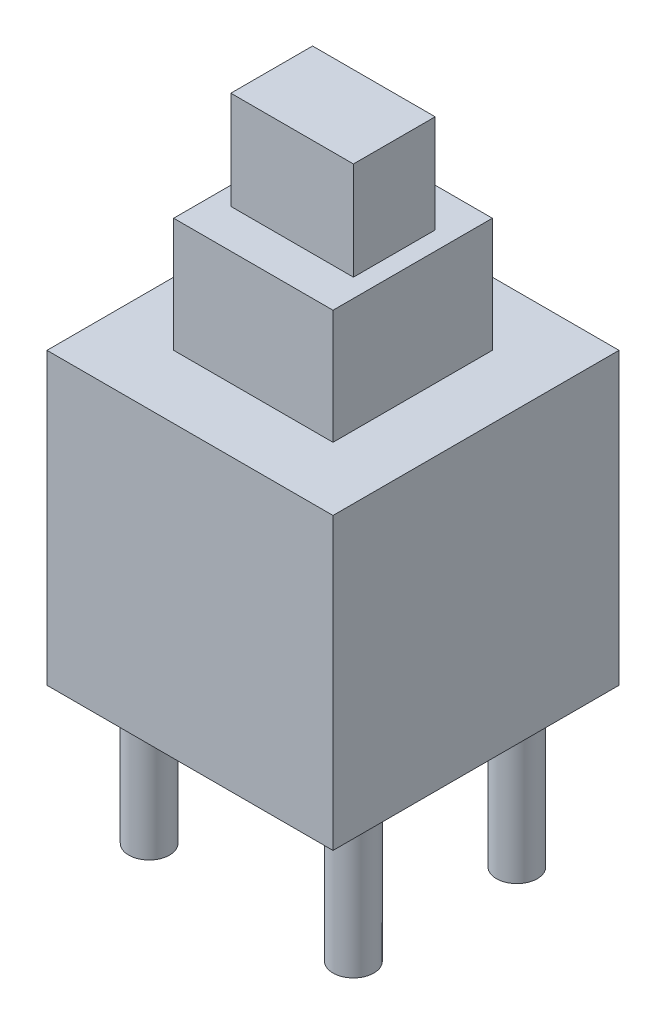
SolidWorks part; units mm, degrees
ref_plane "前视基准面" through (0, 0, 0) normal (0, 0, 1) x (1, 0, 0)
ref_plane "上视基准面" through (0, 0, 0) normal (0, 1, 0) x (1, 0, 0)
ref_plane "右视基准面" through (0, 0, 0) normal (1, 0, 0) x (0, 0, -1)
other "Configuration Table"
sketch "草图1" plane through (0, 0, 0) normal (0, 1, 0) x (1, 0, 0)
  line L1 (0, 0) -> (7, 0)
  line L2 (0, 0) -> (0, 7)
  line L3 (0, 7) -> (7, 7)
  line L4 (7, 0) -> (7, 7)
  dimension "D1" = 7
  dimension "D2" = 7
extrude "凸台-拉伸1" add sketch "草图1" along normal blind 7.1
sketch "草图2" plane through (0, 7.1, 0) normal (0, 1, 0) x (1, 0, 0)
  line L0 (3.5, 7) -> (3.5, 0) construction
  line L1 (7, 7) -> (0, 7) construction
  line L2 (0, 0) -> (7, 0) construction
  line L3 (1.55, 5.45) -> (5.45, 1.55) construction
  line L4 (1.55, 5.45) -> (5.45, 5.45)
  line L5 (1.55, 5.45) -> (1.55, 1.55)
  line L6 (1.55, 1.55) -> (5.45, 1.55)
  line L7 (5.45, 5.45) -> (5.45, 1.55)
  point P10 (3.5, 3.5)
  dimension "D1" = 3.9
extrude "凸台-拉伸2" add sketch "草图2" along normal blind 2.8
sketch "草图3" plane through (0, 0, 0) normal (0, -1, 0) x (1, 0, 0)
  line L0 (3.5, 0) -> (3.5, -7) construction
  line L1 (0, 0) -> (7, 0) construction
  line L2 (7, -7) -> (0, -7) construction
  line L3 (0, -3.5) -> (7, -3.5) construction
  line L4 (0, -7) -> (0, 0) construction
  line L5 (7, 0) -> (7, -7) construction
  circle A0 centre (1, -1.5) radius 0.5
  circle A1 centre (6, -1.5) radius 0.5
  circle A2 centre (6, -5.5) radius 0.5
  circle A3 centre (1, -5.5) radius 0.5
  dimension "D1" = 1
  dimension "D2" = 5
  dimension "D3" = 4
extrude "凸台-拉伸3" add sketch "草图3" along normal blind 3.6
sketch "草图4" plane through (0, 9.9, 0) normal (0, 1, 0) x (1, 0, 0)
  line L0 (3.5, 5.45) -> (3.5, 4.5) construction
  line L1 (2, 4.5) -> (5, 4.5)
  line L2 (2, 4.5) -> (2, 2.5)
  line L3 (2, 2.5) -> (5, 2.5)
  line L4 (5, 4.5) -> (5, 2.5)
  line L5 (5.45, 5.45) -> (1.55, 5.45) construction
  line L6 (1.55, 3.5) -> (2, 3.5) construction
  line L7 (1.55, 5.45) -> (1.55, 1.55) construction
  dimension "D1" = 3
  dimension "D2" = 2
extrude "凸台-拉伸4" add sketch "草图4" along normal offset from surface (2.4 mm away) 12.3 up to face at (1, 0, -6)
